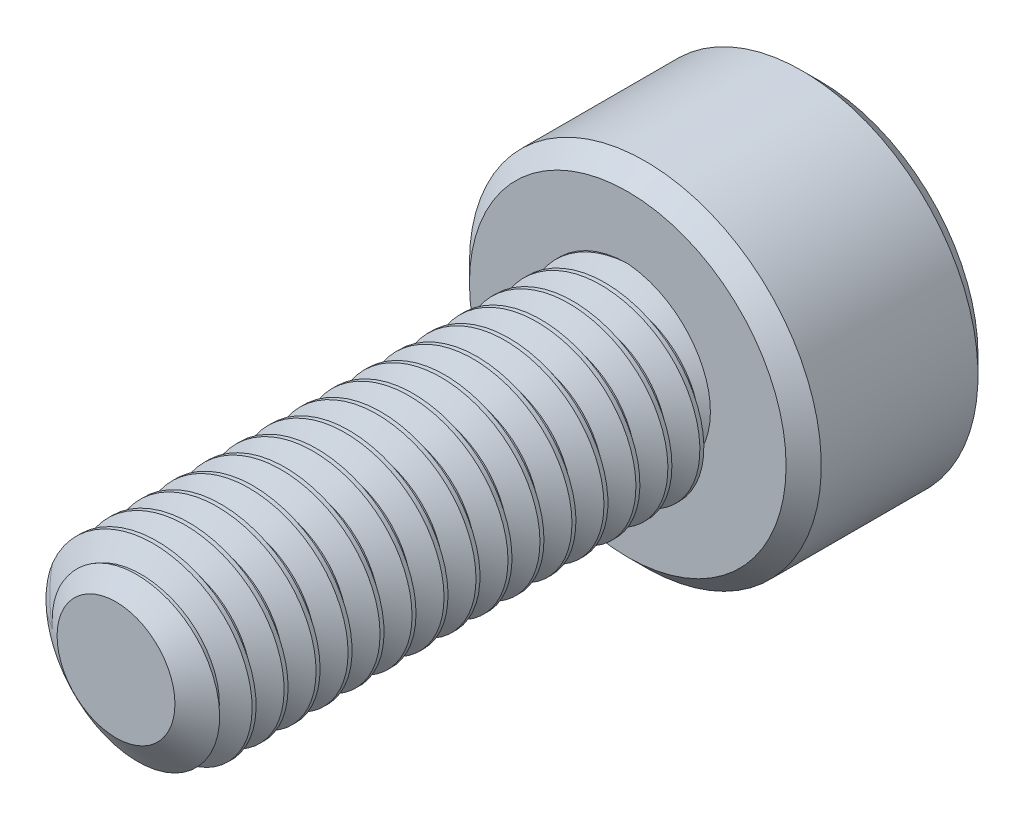
SolidWorks part; units mm, degrees
other "DetailItem1"
ref_plane "Front Plane" through (0, 0, 0) normal (0, 0, 1) x (1, 0, 0)
ref_plane "Top Plane" through (0, 0, 0) normal (0, 1, 0) x (1, 0, 0)
ref_plane "Right Plane" through (0, 0, 0) normal (1, 0, 0) x (0, 0, -1)
sketch "Sketch1" plane through (0, 0, 0) normal (0, 0, 1) x (1, 0, 0)
  circle A0 centre (0, 0) radius 1.5
  dimension "OD" = 3
extrude "Extrude1" add sketch "Sketch1" against normal blind 8
sketch "Sketch2" plane through (0, 0, 0) normal (0, 0, 1) x (1, 0, 0)
  circle A0 centre (0, 0) radius 1.5 construction
  circle A1 centre (0, 0) radius 1.5
curve "Helix/Spiral1" pitch 0.5 height 8.5 radius 1.5 centre (0, 0, 0) axis (0, 0, -1) start towards (0, 1, 0) parameters "pitch"=0.5
sketch "Sketch3" plane through (0, 0, 0) normal (1, 0, 0) x (0, 0, -1)
  line L0 (-0.4375, 1.5) -> (-0.25, 1.1752)
  line L1 (-0.25, 1.1752) -> (-0.1875, 1.1752)
  line L2 (-0.1875, 1.1752) -> (0, 1.5)
  line L3 (-0.4375, 1.5) -> (0, 1.5)
  line L4 (-0.2187, 1.5) -> (-0.2188, 1.1752) construction
  line L5 (-0.3438, 1.3376) -> (-0.0938, 1.3376) construction
  line L6 (0, 1.5) -> (0, -1.5) construction
  dimension "D1" = 0.0625
  dimension "D2" = 0.25
  dimension "D3" = 60
sweep "Cut-Sweep1" cut profiles "Sketch3" path "Helix/Spiral1"
sketch "Sketch4" plane through (0, 0, 0) normal (1, 0, 0) x (0, 0, -1)
  line L0 (0.4053, 1.5) -> (0, 0.9212)
  line L1 (0, 0.9212) -> (0, 1.5)
  line L2 (0.4053, 1.5) -> (0, 1.5)
  line L3 (-0.4375, 1.5) -> (0, 1.5) construction
  line L4 (0, 0) -> (7.0209, 0) construction
  dimension "D1" = 55
  dimension "D2" = 0.254
revolve "Cut-Revolve1" cut sketch "Sketch4" angle 360 about L4
sketch "Sketch6" plane through (0, 0, -8) normal (0, 0, -1) x (-1, 0, 0)
  circle A0 centre (0, 0) radius 2.75
  dimension "head dia" = 5.5
extrude "Extrude2" add sketch "Sketch6" along normal blind 3
sketch "Sketch7" plane through (0, 0, -11) normal (0, 0, -1) x (-1, 0, 0)
  line L1 (0, 1.4434) -> (-1.25, 0.7217)
  line L2 (-1.25, 0.7217) -> (-1.25, -0.7217)
  line L3 (-1.25, -0.7217) -> (0, -1.4434)
  line L4 (0, -1.4434) -> (1.25, -0.7217)
  line L5 (1.25, -0.7217) -> (1.25, 0.7217)
  line L6 (1.25, 0.7217) -> (0, 1.4434)
  circle A0 centre (0, 0) radius 1.25 construction
  dimension "hex dia" = 2.5
extrude "Cut-Extrude1" cut sketch "Sketch7" against normal blind 1.875
sketch "Sketch8" plane through (0, 0, -11) normal (0, 0, -1) x (-1, 0, 0)
  circle A0 centre (0, 0) radius 1.4434
extrude "Cut-Extrude2" cut sketch "Sketch8" against normal through all draft 45
chamfer "Chamfer1" distance 0.275 angle 45 2 edges at (-2.75, 0, -11) (-2.75, 0, -8)
sketch "Sketch10" plane through (0, 0, -8) normal (0, 0, 1) x (1, 0, 0)
  circle A1 centre (0, 0) radius 1.5
  circle A2 centre (0, 0) radius 1.5
  dimension "D1" = 0
ref_plane "Plane1" through (0, 0, 0) normal (0, 0, 1) x (1, 0, 0)
extrude "partial thread" [suppressed] add sketch "Sketch10" along normal up to surface (4 mm away) separate body up to plane "Plane1"
chamfer "Chamfer2" [suppressed] distance 0.06 angle 45
combine bodies "Combine1" [suppressed] operation type add bodies to combine 107 108
sketch "Sketch9" plane through (0, 0, 0) normal (1, 0, 0) x (0, 0, -1)
  line L0 (0, 1.5) -> (0, -1.5) construction
  line L1 (1.25, 1.5) -> (1.25, -1.5) construction
  dimension "D1" = 1.25
equation "\"D3@Helix/Spiral1\" = \"screw length@Extrude1\"+\"pitch@Helix/Spiral1\""
equation "\"D1@Sketch3\" = \"pitch@Helix/Spiral1\"*.125"
equation "\"D2@Sketch3\" = \"pitch@Helix/Spiral1\"*.5"
equation "\"D1@Cut-Extrude1\" = \"hex dia@Sketch7\"*.75"
equation "\"D1@Chamfer1\" = \"head dia@Sketch6\"*.05"
equation "\"D1@Sketch9\" = \"pitch@Helix/Spiral1\"*2.5"
equation "\"D1@Chamfer2\"=\"OD@Sketch1\"*.02"
